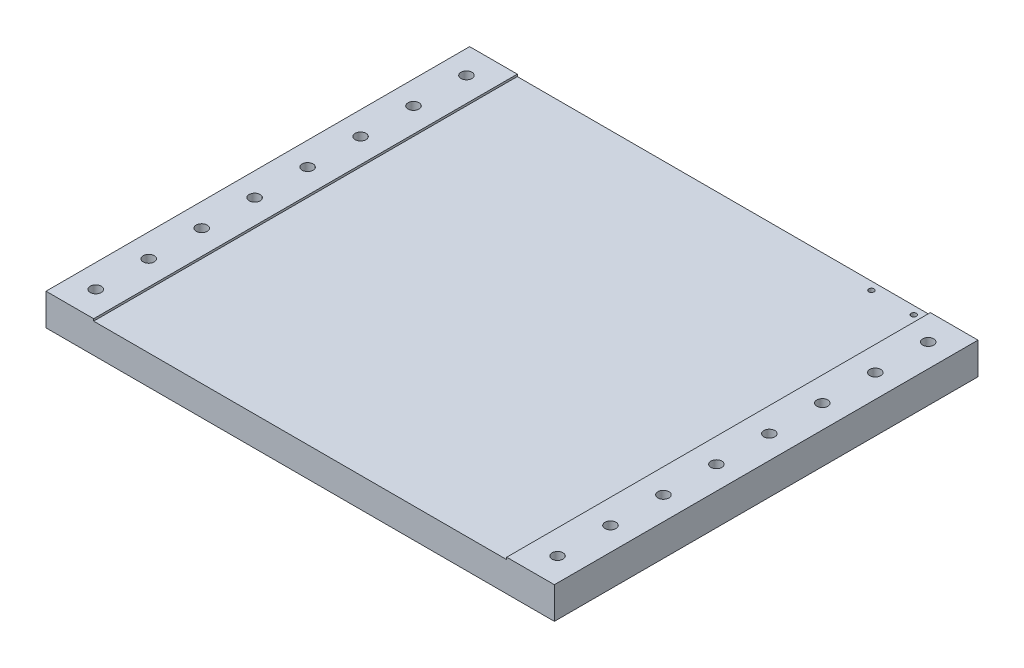
SolidWorks part; units mm, degrees
ref_plane "Front Plane" through (0, 0, 0) normal (0, 0, 1) x (1, 0, 0)
ref_plane "Top Plane" through (0, 0, 0) normal (0, 1, 0) x (1, 0, 0)
ref_plane "Right Plane" through (0, 0, 0) normal (1, 0, 0) x (0, 0, -1)
sketch "Sketch1" plane through (0, 0, 0) normal (0, 1, 0) x (1, 0, 0)
  line L1 (-120, -100) -> (120, -100)
  line L2 (-120, -100) -> (-120, 100)
  line L3 (-120, 100) -> (120, 100)
  line L4 (120, -100) -> (120, 100)
  line L5 (-120, -100) -> (120, 100) construction
  line L6 (-120, 100) -> (120, -100) construction
  point P0 (0, 0)
  dimension "D1" = 240
  dimension "D2" = 200
extrude "Boss-Extrude1" add sketch "Sketch1" along normal mid plane 15
sketch "Sketch3" plane through (0, 7.5, 0) normal (0, 1, 0) x (1, 0, 0)
  line L1 (-92.5, -105) -> (92.5, -105)
  line L2 (-97.5, -100) -> (-97.5, 100)
  line L3 (-92.5, 105) -> (92.5, 105)
  line L4 (97.5, -100) -> (97.5, 100)
  line L5 (-97.5, -105) -> (97.5, 105) construction
  line L6 (-97.5, 105) -> (97.5, -105) construction
  arc A0 (-92.5, -105) -> (-97.5, -100) centre (-92.5, -100) cw
  arc A1 (97.5, -100) -> (92.5, -105) centre (92.5, -100) cw
  arc A2 (97.5, 100) -> (92.5, 105) centre (92.5, 100) ccw
  arc A3 (-92.5, 105) -> (-97.5, 100) centre (-92.5, 100) ccw
  point P0 (0, 0)
  dimension "D3" = 5
  dimension "D1" = 195
  dimension "D2" = 210
extrude "Cut-Extrude2" cut sketch "Sketch3" against normal blind 1
sketch "Sketch4" plane through (0, 7.5, 0) normal (0, 1, 0) x (1, 0, 0)
  line L0 (-109, -1033.7087) -> (-109, 48966.2913) construction
  line L1 (109, -1052.3781) -> (109, 48947.6219) construction
  line L2 (-1012.9649, 87.5) -> (48987.0351, 87.5) construction
  line L3 (-97.5, 100) -> (97.5, 100) construction
  line L4 (-120, 100) -> (-120, -100) construction
  line L5 (120, -100) -> (120, 100) construction
  circle A0 centre (-109, 87.5) radius 2.6
  circle A1 centre (109, 87.5) radius 2.6
  dimension "D4" = 5.2
  dimension "D5" = 5.2
  dimension "D1" = 12.5
  dimension "D2" = 11
  dimension "D3" = 11
extrude "Cut-Extrude3" cut sketch "Sketch4" against normal through all
pattern_linear "LPattern1" count 8 spacing 25 along (0, 0, 1) of "Cut-Extrude3"
hole_wizard "M3x0.5 Tapped Hole1" positions "Sketch7" profile "Sketch6" tap size "M3x0.5" standard "ANSI Metric"
sketch "Sketch7" plane through (0, 6.5, 0) normal (0, 1, 0) x (1, 0, 0)
  line L0 (97.5, -100) -> (97.5, 100) construction
  line L1 (-97.5, 100) -> (97.5, 100) construction
  point P0 (93.5, 96.2)
  point P2 (73.5, 96.2)
  dimension "D1" = 4
  dimension "D2" = 20
  dimension "D3" = 3.8
  dimension "D4" = 3.8
sketch "Sketch6" plane through (93.5, 6.5, -96.2) normal (1, 0, 0) x (0, 0, 1)
  line L0 (0, 0) -> (0, 9.2511)
  line L1 (0, 9.2511) -> (1.25, 8.5)
  line L2 (1.25, 8.5) -> (1.25, 0)
  line L5 (1.25, 0) -> (0, 0)
  line L10 (0, 9.2511) -> (-1.25, 8.5) construction
  line L11 (0, -6.35) -> (0, 107.95) construction
  dimension "Tap Drill Dia." = 2.5
  dimension "Tap Drill Depth" = 8.5
  dimension "Drill Angle" = 118
cosmetic thread "Hole Thread1" parameters "D1"=6, "D2"=3
cosmetic thread "Hole Thread2" parameters "D1"=6, "D2"=3
